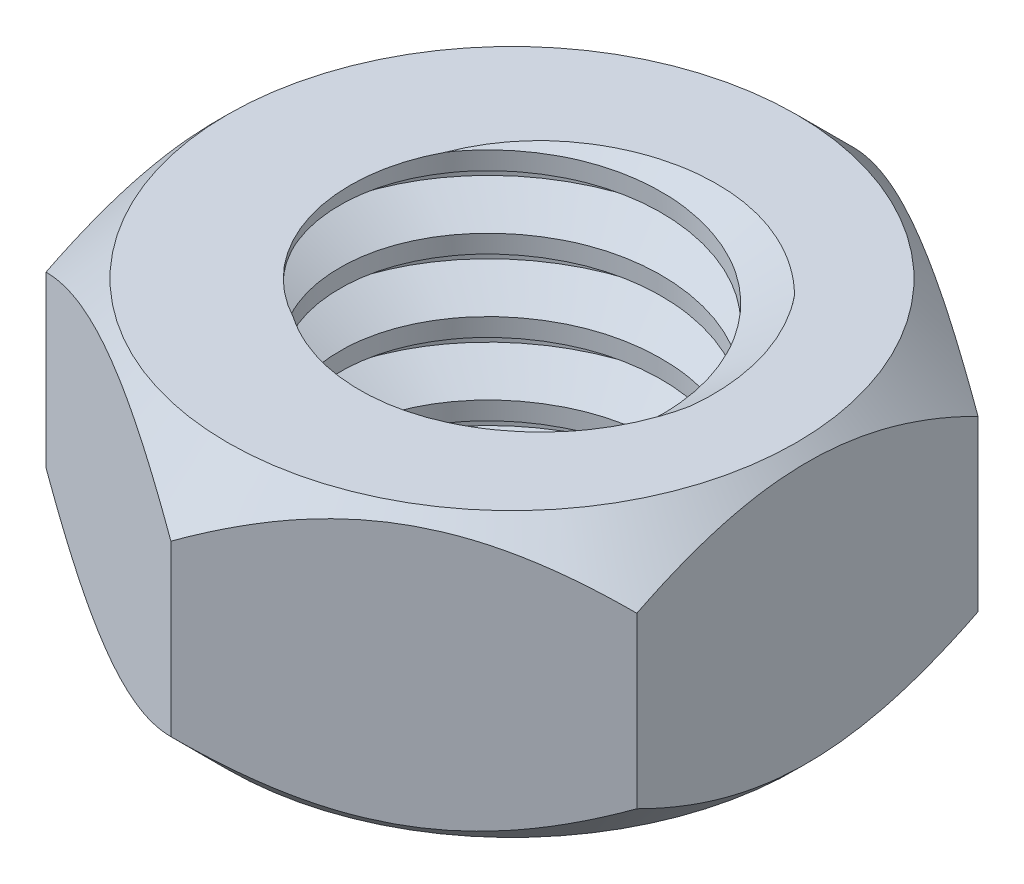
SolidWorks part; units mm, degrees
ref_plane "Front Plane" through (0, 0, 0) normal (0, 0, 1) x (1, 0, 0)
ref_plane "Top Plane" through (0, 0, 0) normal (0, 1, 0) x (1, 0, 0)
ref_plane "Right Plane" through (0, 0, 0) normal (1, 0, 0) x (0, 0, -1)
sketch "Sketch1" plane through (0, 0, 0) normal (0, 1, 0) x (1, 0, 0)
  circle A0 centre (0, 0) radius 1.4224
  circle A1 centre (0, 0) radius 3
  dimension "D1" = 2.8448
  dimension "D2" = 6
extrude "Boss-Extrude1" add sketch "Sketch1" along normal blind 2.4892
chamfer "Chamfer1" distance 0.5 angle 45 2 edges at (0, 0, 3) (0, 2.4892, 3)
sketch "Sketch2" plane through (0, 2.4892, 0) normal (0, 1, 0) x (1, 0, 0)
  line L1 (0, 3) -> (-2.5981, 1.5)
  line L2 (-2.5981, 1.5) -> (-2.5981, -1.5)
  line L3 (-2.5981, -1.5) -> (0, -3)
  line L4 (0, -3) -> (2.5981, -1.5)
  line L5 (2.5981, -1.5) -> (2.5981, 1.5)
  line L6 (2.5981, 1.5) -> (0, 3)
  circle A0 centre (0, 0) radius 3 construction
  circle A1 centre (0, 0) radius 3 construction
  circle A2 centre (0, 0) radius 4
  dimension "D1" = 8
extrude "Cut-Extrude1" cut sketch "Sketch2" against normal through all
ref_plane "Plane3" through (0, 10, 0) normal (0, 1, 0) x (1, 0, 0)
thread "Thread3" pitch 0.635 method cut trim with start face yes trim with end face yes profile "Thread Profile3" start angle 0, offset 0, length 0, pitch 0.635, diameter 2.8448
ref_plane "Plane4" through (-1.4224, 10, 0) normal (0, 0, 1) x (-1, 0, 0)
sketch "Thread Profile3" plane through (-1.4224, 10, 0) normal (0, 0, 1) x (-1, 0, 0)
  line L0 (0, 0) -> (0, 0.635) construction
  line L1 (0, 0) -> (0.3437, 0.1984)
  line L2 (0.3437, 0.1984) -> (0.3437, 0.2778)
  line L3 (0.3437, 0.2778) -> (0, 0.4762)
  line L4 (0.3437, 0.2381) -> (0, 0.2381) construction
  line L11 (0, 0) -> (0, 0.4762)
  point P2 (0, 0)
  dimension "Pitch" = 0.635
  dimension "Profile_Angle" = 60
  dimension "Profile_Land" = 0.0794
  dimension "Profile_Height" = 0.3437
